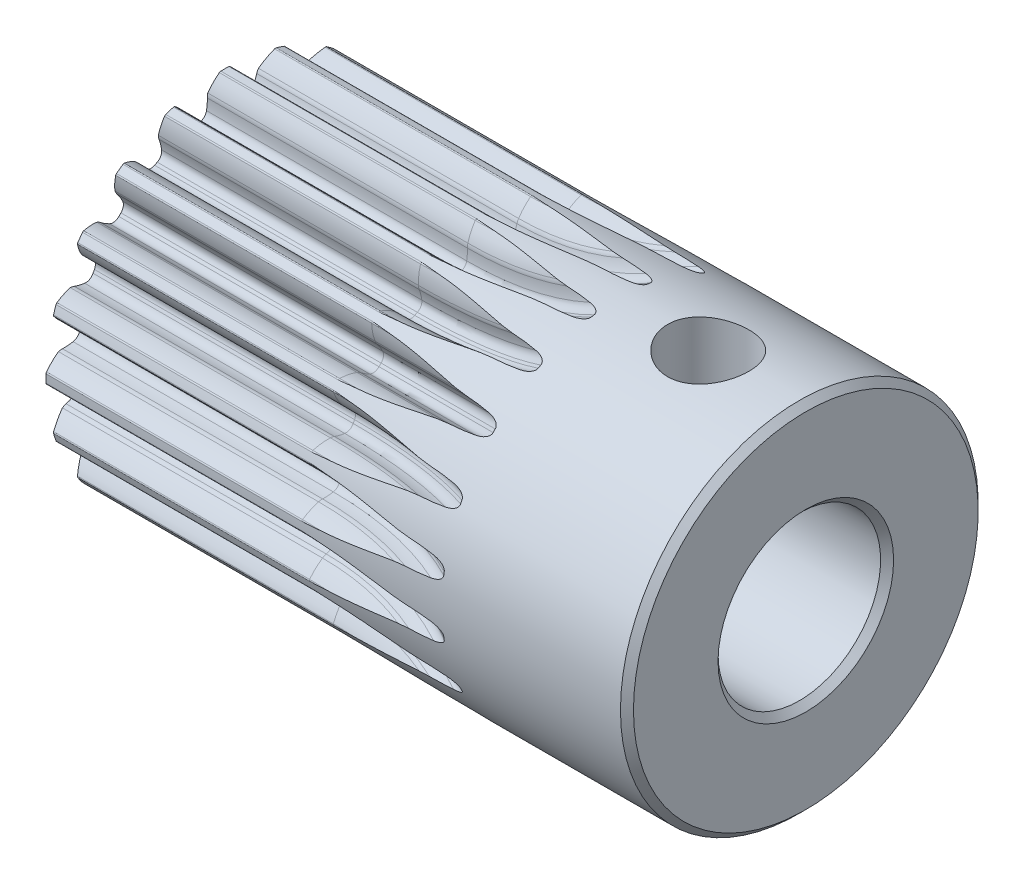
SolidWorks part; units mm, degrees
ref_plane "Front Plane" through (0, 0, 0) normal (0, 0, 1) x (1, 0, 0)
ref_plane "Top Plane" through (0, 0, 0) normal (0, 1, 0) x (1, 0, 0)
ref_plane "Right Plane" through (0, 0, 0) normal (1, 0, 0) x (0, 0, -1)
sketch "Sketch1" plane through (0, 0, 0) normal (0, 0, 1) x (1, 0, 0)
  line L0 (0.134, 5.5) -> (0, 5)
  line L1 (0.134, 5.5) -> (18, 5.5)
  line L2 (0, 5) -> (0, 2.5)
  line L3 (0, 2.5) -> (18, 2.5)
  line L4 (18, 5.5) -> (18, 2.5)
  line L5 (0, 5) -> (18, 5) construction
  line L6 (0, 0) -> (18, 0) construction
  line L7 (0, 4.375) -> (18, 4.375) construction
  line L8 (0, -5) -> (18, -5) construction
  line L9 (0, -4.375) -> (18, -4.375) construction
  dimension "D_s" = 10
  dimension "G" = 8.75
  dimension "H" = 11
  dimension "D1" = 15
  dimension "D2" = 0.5
  dimension "L" = 18
  dimension "P" = 5
revolve "Revolve1" add sketch "Sketch1" angle 360 about L6
chamfer "Chamfer1" distance 0.2 angle 45 1 edges at (18, 0, 5.5)
chamfer "Chamfer1" distance 0.2 angle 45 2 edges at (0, 0, 2.5) (18, 0, 2.5)
ref_plane "Plane1" through (0, 0, 0) normal (0, 0.1564, 0.9877) x (1, 0, 0)
sketch "Sketch2" [suppressed] plane through (0, 0, 0) normal (0, 0.2079, 0.9781) x (1, 0, 0)
  line L0 (8, 4.25) -> (0, 4.25)
  line L1 (0, 0) -> (18, 0) construction
  line L2 (0, 4.25) -> (0, 4.5)
  line L3 (0, 4.5) -> (10.0827, 4.5)
  line L5 (18, -4.3) -> (18, 4.3) construction
  arc A0 (8, 4.25) -> (10.0827, 4.5) centre (8, 13.05) ccw
  dimension "D" = 11
  dimension "H" = 11
  dimension "MSM_4" = 8.8
  dimension "B" = 8
revolve "Cut-Revolve1" [suppressed] cut sketch "Sketch2" angle 360 about L1
sketch "Sketch3" plane through (0, 0, 0) normal (-1, 0, 0) x (0, 0, 1)
  line L0 (0, 0) -> (0, 5.5) construction
  line L1 (0, 0) -> (-0.8604, 5.4323) construction
  line L2 (0, 0) -> (-0.4315, 5.483) construction
  line L3 (-0.2509, 5.4943) -> (-0.5718, 4.3375) construction
  arc A0 (-0.1642, 5.4767) -> (-0.3923, 4.9846) centre (1.2138, 4.5392) ccw
  circle A1 centre (0, 0) radius 5 construction
  circle A2 centre (0, 4.8758) radius 0.4071 construction
  arc A3 (-0.6392, 4.3281) -> (-0.7295, 4.3137) centre (0, 0) ccw
  arc A4 (-0.124, 5.4986) -> (-0.1642, 5.4767) centre (-0.1229, 5.4486) ccw
  arc A5 (-0.3923, 4.9846) -> (-0.4068, 4.8603) centre (0, 4.8758) ccw
  arc A6 (-0.6392, 4.3281) -> (-0.4296, 4.5315) centre (-0.6757, 4.5754) ccw
  arc A8 (-0.4296, 4.5315) -> (-0.4068, 4.8603) centre (-1.9442, 4.8017) ccw
  arc A9 (-0.124, 5.4986) -> (-1.5812, 5.2678) centre (0, 0) ccw
  circle A10 centre (0, 0) radius 4.375 construction
  circle A11 centre (0, 0) radius 5.5 construction
  arc A12 (-0.7295, 4.3137) -> (-0.9917, 4.4424) centre (-0.7712, 4.5602) cw
  arc A13 (-0.9917, 4.4424) -> (-1.115, 4.7481) centre (0.3652, 5.1674) cw
  arc A14 (-1.1672, 4.8618) -> (-1.115, 4.7481) centre (-1.5067, 4.6372) cw
  arc A15 (-1.5362, 5.2594) -> (-1.1672, 4.8618) centre (-2.557, 3.942) cw
  arc A16 (-1.5812, 5.2678) -> (-1.5362, 5.2594) centre (-1.5669, 5.2199) cw
  point P10 (-0.3923, 4.9846)
  point P34 (-0.4737, 4.3493)
  dimension "D_s" = 10
  dimension "G" = 8.75
  dimension "D4" = 0.05
  dimension "D" = 11
  dimension "D5" = 1.6667
  dimension "D6" = 1.5385
  dimension "D7" = 0.25
  dimension "D1" = 4.5
  dimension "D2" = 9
  dimension "D3" = 20
  dimension "D8" = 0.425
sketch "Sketch4" plane through (0, 0, 0) normal (0, 0.1564, 0.9877) x (1, 0, 0)
  line L0 (8, 4.375) -> (0, 4.375)
  line L1 (0, 0) -> (18, 0) construction
  line L2 (18, -5.5) -> (18, 5.5) construction
  line L3 (18, -5.3) -> (18, 5.3) construction
  arc A0 (8, 4.375) -> (12.3052, 5.5) centre (8, 13.175) ccw
  dimension "MSM_4" = 8.8
  dimension "L1_s" = 10
  dimension "H" = 11
  dimension "B" = 8
sweep "Cut-Sweep1" cut profiles "Sketch3" path "Sketch4"
pattern_circular "CirPattern1" count 20 over 360 about axis through (0, 0, 0) along (1, 0, 0) of "Cut-Sweep1"
ref_plane "Plane2" through (0, 5.5, 0) normal (0, 1, 0) x (1, 0, 0)
hole_wizard "Tapped Hole1" positions "Sketch6" profile "Sketch5" tap size "M3x0.5" standard "JIS" end condition up to next
sketch "Sketch6" plane through (0, 5.5, 0) normal (0, 1, 0) x (1, 0, 0)
  line L0 (0, 0) -> (18, 0) construction
  line L2 (18, -5.3) -> (18, 5.3) construction
  point P0 (15, 0)
  dimension "L2_s" = 3
sketch "Sketch5" plane through (15, 5.5, 0) normal (1, 0, 0) x (0, 0, 1)
  line L0 (0, 0) -> (0, 3)
  line L1 (0, 3) -> (1.25, 3)
  line L2 (1.25, 3) -> (1.25, 0)
  line L5 (1.25, 0) -> (0, 0)
  line L11 (0, 0) -> (0, 3) construction
  dimension "Thru Tap Drill Dia." = 2.5
  dimension "Thru Tap Drill Depth" = 3
cosmetic thread "Hole Thread1" parameters "M"=3
pattern_circular "CirPattern2" [suppressed] count 2 over 90
pattern_circular "CirPattern3" [suppressed] count 2 every 120
sketch "Sketch7" [suppressed] plane through (0, 0, 0) normal (0, 0, 1) x (1, 0, 0)
  line L0 (0.134, 4.5) -> (18, 4.5) construction
  line L1 (13.5, 4.5) -> (17.8, 4.5)
  line L2 (13.5, 4.5) -> (13.5, 1.5)
  line L3 (13.5, 1.5) -> (17.8, 1.5)
  line L4 (17.8, 4.5) -> (17.8, 1.5)
  line L20 (18, -4.3) -> (18, 4.3) construction
  line L27 (0, 1.5) -> (18, 1.5) construction
  line L38 (0, 0) -> (18, 0) construction
  line L39 (17.8, 4.5) -> (17.8, -4.5) construction
  dimension "D1" = 4.5
revolve "Revolve2" [suppressed] add sketch "Sketch7" angle 360 about L38
hole_wizard "Tapped Hole2" [suppressed] positions "Sketch9" profile "Sketch8" tap size "M4x0.7" standard "JIS"
sketch "Sketch9" [suppressed] plane through (0, 4.5, 0) normal (0, 1, 0) x (1, 0, 0)
  line L1 (0, 0) -> (18, 0) construction
  line L3 (18, -4.3) -> (18, 4.3) construction
  point P0 (15, 0)
  dimension "L2_s" = 3
sketch "Sketch8" [suppressed] plane through (15, 4.5, 0) normal (1, 0, 0) x (0, 0, 1)
  line L0 (0, 0) -> (0, 6.15)
  line L1 (0, 6.15) -> (1.65, 6.15)
  line L2 (1.65, 6.15) -> (1.65, 0)
  line L5 (1.65, 0) -> (0, 0)
  line L11 (0, 0) -> (0, 6.15) construction
  dimension "Thru Tap Drill Dia." = 3.3
  dimension "Thru Tap Drill Depth" = 6.15
cosmetic thread "Hole Thread2" [suppressed] parameters "TPC"=4
pattern_circular "CirPattern4" [suppressed] count 2 over 90
pattern_circular "CirPattern5" [suppressed] count 2 over 120
equation "\"D1@Plane1\" = ( 360 / \"Teeth@CirPattern1\" ) / 2"
equation "\"D2@Sketch3\" = ( 360 / \"Teeth@CirPattern1\" ) / 2"
equation "\"D1@Sketch3\"=360/\"Teeth@CirPattern1\"/4"
equation "\"Plane dim\"= \"H@Sketch1\" * 0.5"
equation "\"Module\"= 0.5"
equation "\"D4@Sketch3\"=0.1 * \"Module\""
equation "\"Cut-Revolve1\"  = if ( \"H@Sketch1\" = \"D@Sketch2\" , \"suppressed\" , \"unsuppressed\" )"
equation "\"Sketch2\" = if ( \"H@Sketch1\" = \"D@Sketch2\" , \"suppressed\" , \"unsuppressed\" )"
equation "\"D5@Sketch3\"=\"Teeth@CirPattern1\"/\"MSM_1\""
equation "\"D6@Sketch3\"=\"Teeth@CirPattern1\"/\"MSM_2\""
equation "\"D7@Sketch3\"=0.5*\"Module\""
equation "\"D8@Sketch3\"=0.85*\"Module\""
equation "\"D1@Sketch7\"=\"L2_s@Sketch6\"+\"M@Hole Thread1\"/2"
equation "\"MSM_1\"=12"
equation "\"MSM_2\"=13"
